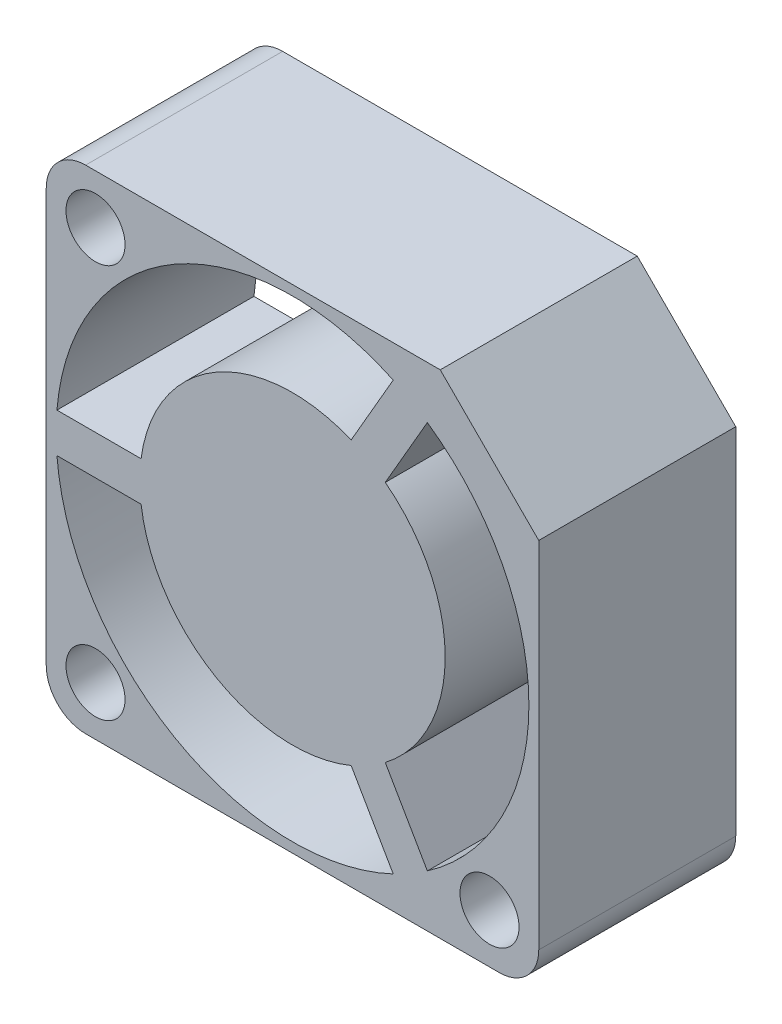
SolidWorks part; units mm, degrees
ref_plane "Front" through (0, 0, 0) normal (0, 0, 1) x (1, 0, 0)
ref_plane "Top" through (0, 0, 0) normal (0, 1, 0) x (1, 0, 0)
ref_plane "Right" through (0, 0, 0) normal (1, 0, 0) x (0, 0, -1)
sketch "Szkic1" plane through (0, 0, 0) normal (0, 0, 1) x (1, 0, 0)
  line L0 (-7.6852, 1) -> (-11.9583, 1)
  line L1 (-10.5, 12.5) -> (7.5, 12.5)
  line L2 (-12.5, 10.5) -> (-12.5, -10.5)
  line L3 (-10.5, -12.5) -> (10.5, -12.5)
  line L4 (12.5, 7.5) -> (12.5, -10.5)
  line L5 (-11.9583, -1) -> (-7.6852, -1)
  line L6 (4.7086, 6.1556) -> (6.8452, 9.8562)
  line L7 (5.1131, 10.8562) -> (2.9766, 7.1556)
  line L8 (2.9766, -7.1556) -> (5.1131, -10.8562)
  line L9 (6.8452, -9.8562) -> (4.7086, -6.1556)
  line L10 (7.5, 12.5) -> (12.5, 7.5)
  arc A0 (-11.9583, -1) -> (5.1131, -10.8562) centre (0, 0) ccw
  arc A1 (12.5, -10.5) -> (10.5, -12.5) centre (10.5, -10.5) cw
  arc A2 (-10.5, -12.5) -> (-12.5, -10.5) centre (-10.5, -10.5) cw
  arc A3 (-12.5, 10.5) -> (-10.5, 12.5) centre (-10.5, 10.5) cw
  circle A5 centre (-10, 10) radius 1.5
  circle A6 centre (-10, -10) radius 1.5
  circle A7 centre (10, -10) radius 1.5
  arc A8 (-7.6852, -1) -> (2.9766, -7.1556) centre (0, 0) ccw
  arc A9 (2.9766, 7.1556) -> (-7.6852, 1) centre (0, 0) ccw
  arc A10 (5.1131, 10.8562) -> (-11.9583, 1) centre (0, 0) ccw
  arc A11 (4.7086, -6.1556) -> (4.7086, 6.1556) centre (0, 0) ccw
  arc A12 (6.8452, -9.8562) -> (6.8452, 9.8562) centre (0, 0) ccw
  point P9 (12.5, -12.5)
  point P12 (-12.5, -12.5)
  point P15 (-12.5, 12.5)
  point P29 (12.5, 12.5)
  point P38 (0, 0)
  dimension "D4" = 24
  dimension "D6" = 2
  dimension "D7" = 3
  dimension "D8" = 3
  dimension "D9" = 3
  dimension "D16" = 15.5
  dimension "D1" = 25
  dimension "D2" = 25
  dimension "D3" = 12.5
  dimension "D5" = 12.5
  dimension "D10" = 2.5
  dimension "D11" = 2.5
  dimension "D12" = 2.5
  dimension "D13" = 2.5
  dimension "D14" = 2.5
  dimension "D15" = 2.5
  dimension "D17" = 11.5
  dimension "D18" = 11.5
  dimension "D19" = 3
extrude "Dodanie-wyciągnięcie1" add sketch "Szkic1" along normal blind 10
